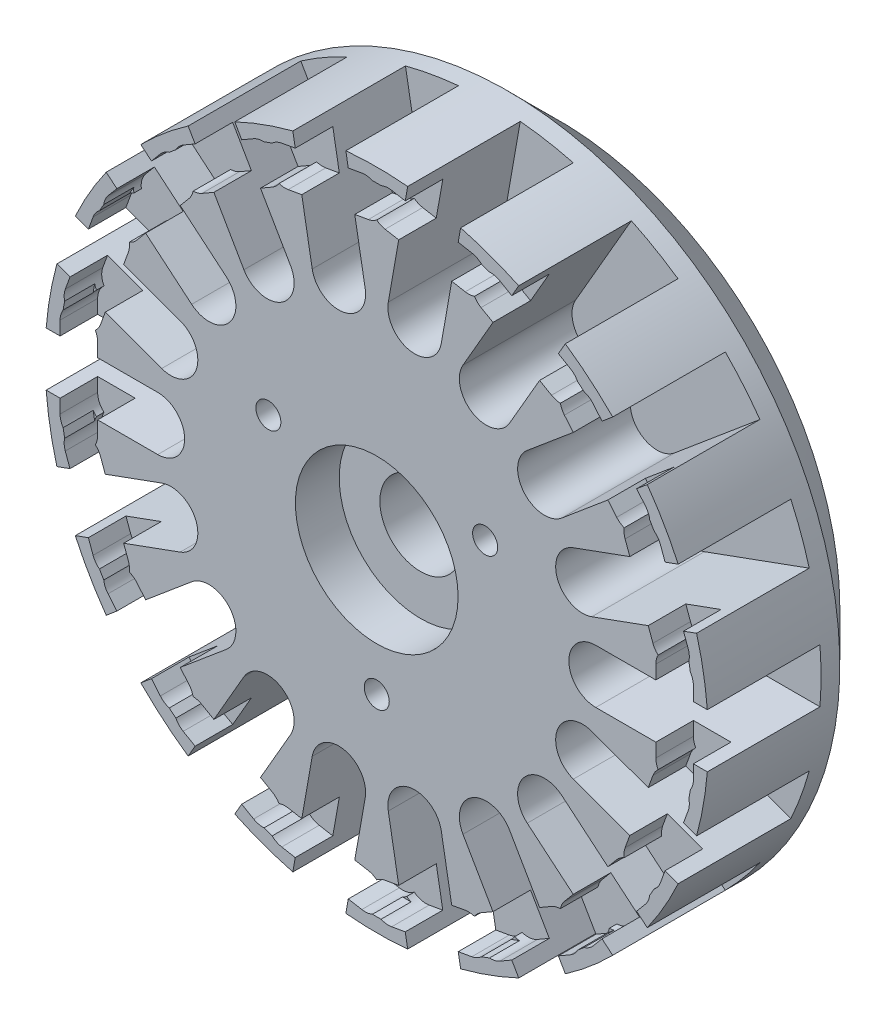
SolidWorks part; units mm, degrees
ref_plane "Front" through (0, 0, 0) normal (0, 0, 1) x (1, 0, 0)
ref_plane "Top" through (0, 0, 0) normal (0, 1, 0) x (1, 0, 0)
ref_plane "Right" through (0, 0, 0) normal (1, 0, 0) x (0, 0, -1)
sketch "Sketch1" plane through (0, 0, 0) normal (0, 0, 1) x (1, 0, 0)
  circle A0 centre (0, 0) radius 26.5
  dimension "D1" = 53
extrude "Extrude1" add sketch "Sketch1" along normal blind 10.5
sketch "Sketch2" plane through (0, 0, 10.5) normal (0, 0, 1) x (1, 0, 0)
  line L0 (32.5, 2.15) -> (17.5, 2.15)
  line L2 (17.5, -2.15) -> (32.5, -2.15)
  line L3 (32.5, -2.15) -> (32.5, 2.15)
  arc A1 (17.5, 2.15) -> (17.5, -2.15) centre (17.5, 0) ccw
  dimension "D1" = 17.5
  dimension "D2" = 4.3
  dimension "D3" = 15
extrude "Extrude2" cut sketch "Sketch2" against normal blind 9
pattern_circular "CirPattern1" count 18 over 360 about axis through (0, 0, 10.5) along (0, 0, -1) of "Extrude2"
sketch "Sketch11" plane through (0, 0, 0) normal (0, 0, -1) x (-1, 0, 0)
  circle A0 centre (0, 0) radius 3.25
  dimension "D1" = 6.5
extrude "Extrude5" cut sketch "Sketch11" against normal up to surface (10.5 mm away) up to face at (0, 0, 10.5)
sketch "Sketch12" plane through (0, 0, 0) normal (0, 0, -1) x (-1, 0, 0)
  circle A0 centre (0, 0) radius 6.5
  dimension "D1" = 13
extrude "Extrude6" cut sketch "Sketch12" against normal blind 3.5
sketch "Sketch13" plane through (0, 0, 10.5) normal (0, 0, 1) x (1, 0, 0)
  circle A0 centre (0, 0) radius 6.5
  dimension "D1" = 13
extrude "Extrude7" cut sketch "Sketch13" against normal blind 3.5
sketch "Sketch14" plane through (0, 0, 0) normal (1, 0, 0) x (0, 0, -1)
  line L0 (-10.5, 21.799) -> (-10.5, 18.6247) construction
  line L1 (-11.1, 25.3847) -> (-8.1, 25.3847)
  line L2 (-11.1, 25.3847) -> (-11.1, 22.9847)
  line L3 (-11.1, 22.9847) -> (-8.1, 22.9847)
  line L4 (-8.1, 25.3847) -> (-8.1, 22.9847)
  line L5 (-10.5, 26.3847) -> (-1.5, 26.3847) construction
  dimension "D1" = 2.4
  dimension "D2" = 2.4
  dimension "D3" = 3
  dimension "D4" = 1
ref_axis "Axis1" through (0, 0, 10.5) along (0, 0, -1)
revolve "Cut-Revolve1" cut sketch "Sketch14" angle 360 about axis through (0, 0, 10.5) along (0, 0, -1)
sketch "Sketch15" plane through (0, 0, 10.5) normal (0, 0, 1) x (1, 0, 0)
  circle A0 centre (0, -10) radius 1
  dimension "D2" = 2
  dimension "D1" = 10
extrude "Extrude8" cut sketch "Sketch15" against normal blind 8
pattern_circular "CirPattern4" count 3 over 360 about axis through (0, 0, 10.5) along (0, 0, -1) of "Extrude8"
sketch "Sketch16" plane through (0, 0, 0) normal (0, 0, -1) x (-1, 0, 0)
  circle A0 centre (0, 0) radius 26.5
  circle A1 centre (0, 0) radius 18
  dimension "D1" = 36
extrude "Extrude9" add sketch "Sketch16" along normal blind 4
chamfer "Chamfer1" distance 4 angle 45 1 edges at (-26.5, 0, -4)
sketch "Sketch17" plane through (0, 0, -4) normal (0, 0, -1) x (-1, 0, 0)
  line L1 (-2, 17) -> (2, 17)
  line L2 (-2, 17) -> (-2, 22)
  line L3 (-2, 22) -> (2, 22)
  line L4 (2, 17) -> (2, 22)
  dimension "D1" = 2
  dimension "D2" = 2
  dimension "D3" = 17
  dimension "D4" = 5
extrude "Extrude10" cut sketch "Sketch17" against normal up to surface (4 mm away) up to face at (-18, 0, 0)
fillet "Fillet1" radius 2 2 edges at (2, 22, -2) (-2, 22, -2)
pattern_circular "CirPattern5" count 6 over 360 about axis through (0, 0, 0) along (0, 0, 1) of "Extrude10", "Fillet1"
sketch "Sketch19" plane through (0, 0, 0) normal (0, 0, -1) x (-1, 0, 0)
  circle A0 centre (0, 20) radius 0.75
  dimension "D2" = 1.5
  dimension "D1" = 20
extrude "Extrude12" cut sketch "Sketch19" against normal blind 6
hole_wizard "M2.5 Tapped Hole1" positions "3DSketch1" profile "Sketch20" tap size "M2.5" standard "DIN"
sketch3d "3DSketch1"
  line L0 (0, 20, 6) -> (0, 20, 0) construction
  point P0 (0, 20, 0)
sketch "Sketch20" plane through (0, 20, 0) normal (1, 0, 0) x (0, 1, 0)
  line L0 (0, 0) -> (0, 6.6159)
  line L1 (0, 6.6159) -> (1.025, 6)
  line L2 (1.025, 6) -> (1.025, 0)
  line L5 (1.025, 0) -> (0, 0)
  line L10 (0, 6.6159) -> (-1.025, 6) construction
  line L11 (0, -6.35) -> (0, 107.95) construction
  dimension "Tap Drill Dia." = 2.05
  dimension "Tap Drill Depth" = 6
  dimension "Drill Angle" = 118
cosmetic thread "Hole Thread1" parameters "D1"=4.6, "D2"=2.5
pattern_circular "CirPattern6" count 3 over 360 about axis through (0, 0, 0) along (0, 0, 1) of "Extrude12", "M2.5 Tapped Hole1"
sketch "Sketch21" plane through (0, 0, 10.5) normal (0, 0, 1) x (1, 0, 0)
  line L0 (-23.8, -3.25) -> (-23.8, 3.25) construction
  line L1 (-25.3, -3.25) -> (-25.3, 3.25)
  line L2 (-22.3, -3.25) -> (-22.3, 3.25)
  arc A0 (-25.3, -3.25) -> (-22.3, -3.25) centre (-23.8, -3.25) ccw
  arc A1 (-22.3, 3.25) -> (-25.3, 3.25) centre (-23.8, 3.25) ccw
  point P2 (-23.8, 0)
  dimension "D1" = 3
  dimension "D2" = 23.8
  dimension "D3" = 6.5
extrude "Cut-Extrude1" cut sketch "Sketch21" against normal blind 3
pattern_circular "CirPattern7" count 18 over 360 about axis through (0, 0, 10.5) along (0, 0, -1) of "Cut-Extrude1"
